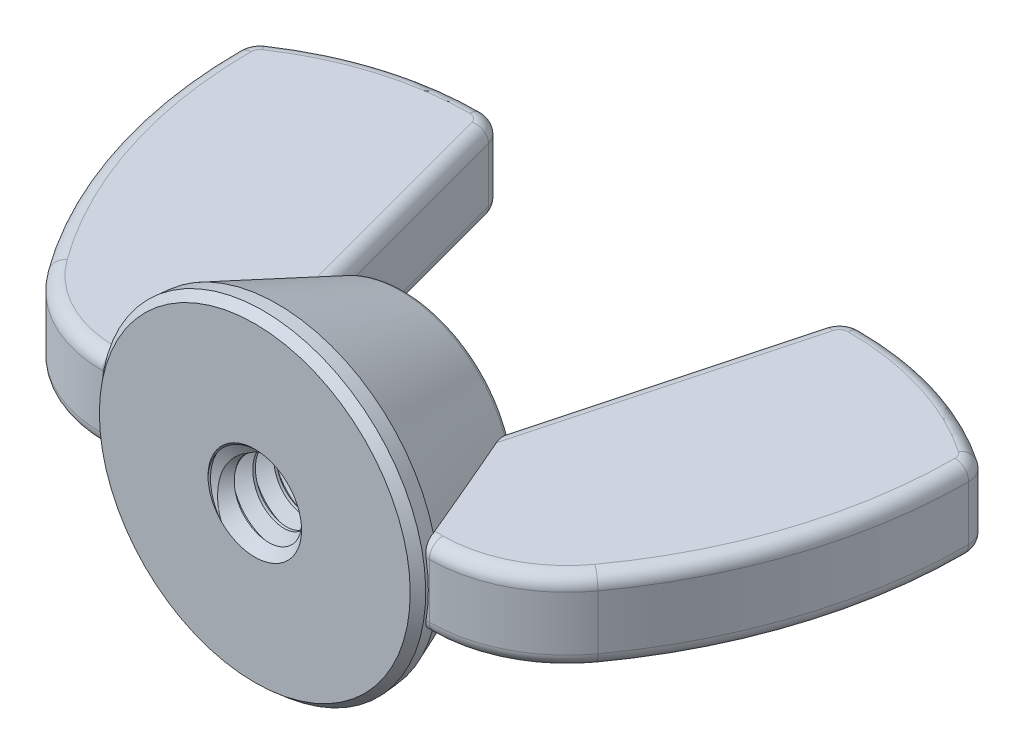
SolidWorks part; units mm, degrees
ref_plane "Front Plane" through (0, 0, 0) normal (0, 0, 1) x (1, 0, 0)
ref_plane "Top Plane" through (0, 0, 0) normal (0, 1, 0) x (1, 0, 0)
ref_plane "Right Plane" through (0, 0, 0) normal (1, 0, 0) x (0, 0, -1)
sketch "Sketch1" plane through (0, 0, 0) normal (0, 0, 1) x (1, 0, 0)
  circle A0 centre (0, 0) radius 1.4224
  circle A1 centre (0, 0) radius 4.9609
  dimension "D1" = 9.9219
sketch "Sketch2" plane through (0, 0, 0) normal (0, 1, 0) x (1, 0, 0)
  line L0 (0, 0) -> (0, 12.7) construction
  line L1 (-1.4224, 0) -> (1.4224, 0) construction
  line L2 (-11.1125, 12.7) -> (11.1125, 12.7) construction
  line L3 (11.1125, 12.7) -> (11.1125, 0) construction
  line L4 (-11.1125, 12.7) -> (-11.1125, 0) construction
  line L5 (-11.1125, 0) -> (11.1125, 0) construction
  line L6 (-3.3816, 4.572) -> (3.3816, 4.572) construction
  line L7 (0, 0) -> (0, 4.572) construction
  line L8 (-4.3144, 0.6858) -> (4.9609, 0.6858) construction
  line L9 (4.9609, 0) -> (4.9609, 4.572) construction
  line L10 (3.0435, 4.572) -> (5.2692, 12.8785)
  line L12 (3.3816, 4.572) -> (3.3816, 0.3429) construction
  line L13 (-4.9609, 0) -> (4.9609, 0) construction
  line L14 (4.9609, 0.6858) -> (3.3816, 4.572) construction
  line L15 (5.2692, 12.8785) -> (11.3534, 11.0184)
  line L16 (11.3534, 11.0184) -> (6.8784, 0.3429)
  line L17 (4.9609, 0.3429) -> (6.8784, 0.3429)
  line L19 (3.0435, 0.3429) -> (4.9609, 0.3429)
  line L20 (-3.0435, 4.572) -> (3.0435, 4.572) construction
  line L21 (3.0435, 4.572) -> (3.0435, 0.3429)
  circle A3 centre (10.4235, 10.5822) radius 0.689 construction
  circle A4 centre (5.7501, 12.011) radius 0.689 construction
  dimension "D6" = 1.378
  dimension "D2" = 4.572
  dimension "D4" = 6.7633
  dimension "D1" = 0.6858
  dimension "D3" = 22.116
  dimension "D5" = 0.3429
  dimension "D8" = 17
  dimension "D9" = 6.087
  dimension "D7" = 15
sketch "Sketch13" plane through (0, 0, 0) normal (0, 1, 0) x (1, 0, 0)
  line L1 (3.0435, 4.572) -> (3.0435, 0.3429) construction
  line L2 (3.0435, 4.572) -> (5.2692, 12.8785) construction
  line L3 (-11.1125, 12.7) -> (11.1125, 12.7) construction
  line L4 (11.1125, 12.7) -> (11.1125, 0) construction
  line L5 (4.9609, 0.3429) -> (6.8784, 0.3429) construction
  line L6 (3.0435, 0.3429) -> (4.9609, 0.3429) construction
  line L7 (0, 0) -> (0, 4.572) construction
  line L8 (-1.4224, 0) -> (1.4224, 0) construction
  line L9 (0, 0) -> (0, 12.7) construction
  line L10 (-3.3816, 4.572) -> (3.3816, 4.572) construction
  line L11 (3.0435, 0.3429) -> (4.9609, 0.3429)
  line L12 (3.0435, 4.572) -> (3.0435, 0.3429)
  line L13 (3.0435, 4.572) -> (5.0845, 12.1893)
  circle A0 centre (10.4235, 10.5822) radius 0.689 construction
  circle A1 centre (5.7501, 12.011) radius 0.689 construction
  arc A5 (11.1125, 10.5822) -> (10.8088, 11.1534) centre (10.4235, 10.5822) ccw
  arc A6 (5.7501, 12.7) -> (5.0845, 12.1893) centre (5.7501, 12.011) ccw
  arc A7 (8.3532, 2.0738) -> (11.1125, 10.5822) centre (-3.3853, 10.5822) ccw
  arc A8 (10.8088, 11.1534) -> (5.7501, 12.7) centre (5.7501, 3.6536) ccw
  arc A10 (4.9609, 0.3429) -> (8.3532, 2.0738) centre (4.9609, 4.5326) ccw
extrude "Extrude2" add sketch "Sketch13" along normal mid plane 2.4805
sketch "Sketch3" plane through (0, 0, 0) normal (0, 0, 1) x (1, 0, 0)
  circle A0 centre (0, 0) radius 4.9609 construction
  circle A1 centre (0, 0) radius 4.9609
extrude "Extrude1" add sketch "Sketch3" against normal up to vertex (0.6858 mm away) draft 5 separate body up to point (4.9609, 0, -0.6858)
sketch "Sketch15" plane through (0, 0, -0.6858) normal (0, 0, -1) x (-1, 0, 0)
  circle A1 centre (0, 0) radius 4.9009
  circle A2 centre (0, 0) radius 4.9009
  dimension "D1" = 0
extrude "Extrude3" add sketch "Sketch15" along normal up to vertex (3.8862 mm away) draft 22.116 up to point (0, 0, -4.572)
fillet "Fillet3" radius 0.254 1 edges at (-3.3216, 0, -4.572)
sketch "Sketch12" plane through (0, 0, -4.572) normal (0, 0, -1) x (-1, 0, 0)
  circle A1 centre (0, 0) radius 4.9009
  circle A2 centre (0, 0) radius 4.9009 construction
  dimension "D1" = 9.8019
sketch "Sketch4" plane through (0, 0, 0) normal (0, 0, 1) x (1, 0, 0)
  circle A0 centre (0, 0) radius 1.4224 construction
  circle A1 centre (0, 0) radius 1.4224
extrude "Cut-Extrude1" cut sketch "Sketch4" against normal through all
sketch "Sketch5" plane through (0, 0, 0) normal (0, 0, 1) x (1, 0, 0)
  circle A0 centre (0, 0) radius 1.4224 construction
  circle A1 centre (0, 0) radius 1.4224
curve "Helix/Spiral1" pitch 0.635 height 7.747 radius 1.4224 centre (0, 0, 0) axis (0, 0, -1) start towards (1, 0, 0) parameters "pitch"=0.635
sketch "Sketch6" plane through (0, 0, 0) normal (0, 1, 0) x (1, 0, 0)
  line L0 (-1.4224, -0.5556) -> (-1.01, -0.3175)
  line L1 (-1.01, -0.3175) -> (-1.01, -0.2381)
  line L2 (-1.01, -0.2381) -> (-1.4224, 0)
  line L3 (-1.4224, -0.5556) -> (-1.4224, 0)
  line L4 (-1.4224, -0.2778) -> (-1.01, -0.2778) construction
  line L5 (-1.2162, -0.4366) -> (-1.2162, -0.1191) construction
  line L6 (-1.4224, 0) -> (1.4224, 0) construction
  dimension "D1" = 60
  dimension "D2" = 0.0794
  dimension "D3" = 0.3175
sweep "Sweep1" add profiles "Sketch6" path "Helix/Spiral1"
sketch "Sketch7" plane through (0, 0, 0) normal (0, 0, 1) x (1, 0, 0)
  circle A1 centre (0, 0) radius 4.9609
  circle A2 centre (0, 0) radius 4.9609
  dimension "D1" = 0
extrude "Cut-Extrude2" cut sketch "Sketch7" along normal through all
ref_plane "Plane1" through (0, 0, -4.572) normal (0, 0, 1) x (1, 0, 0)
sketch "Sketch8" plane through (0, 0, -4.572) normal (0, 0, 1) x (1, 0, 0)
  circle A0 centre (0, 0) radius 4.9009 construction
  circle A2 centre (0, 0) radius 4.9009
extrude "Cut-Extrude3" cut sketch "Sketch8" against normal through all
sketch "Sketch9" plane through (0, 0, 0) normal (0, 0, 1) x (1, 0, 0)
  circle A1 centre (0, 0) radius 1.4224
  circle A2 centre (0, 0) radius 1.4224
  dimension "D1" = 0
extrude "Cut-Extrude4" cut sketch "Sketch9" against normal through all draft 45
sketch "Sketch11" plane through (0, 0, -4.572) normal (0, 0, 1) x (1, 0, 0)
  circle A0 centre (0, 0) radius 1.4224 construction
  circle A1 centre (0, 0) radius 1.3716
  circle A2 centre (0, 0) radius 1.4224 construction
  dimension "D1" = 0.0508
extrude "Cut-Extrude5" cut sketch "Sketch11" along normal through all draft 45
chamfer "Chamfer1" distance 0.2572 angle 45 1 edges at (4.9609, 0, 0) first distance on face at (-4.9009, 0, -0.6858)
fillet "Fillet4" radius 0.4134 14 edges at (4.0022, 1.2402, -0.3429) (6.8651, 1.2402, -0.8006) (5.3306, 1.2402, -12.5576) (8.395, 1.2402, -12.3047) (11.0318, 1.2402, -10.9057) (4.0022, -1.2402, -0.3429) (6.8651, -1.2402, -0.8006) (5.3306, -1.2402, -12.5576) (8.395, -1.2402, -12.3047) (11.0318, -1.2402, -10.9057) (10.4054, 1.2402, -6.1098) (10.4054, -1.2402, -6.1098) (4.064, 1.2402, -8.3807) (4.064, -1.2402, -8.3807)
mirror "Mirror6" about plane through (0, 0, 0) normal (1, 0, 0) of bodies 108 113
combine bodies "Combine2" operation type add bodies to combine 116 108 107
equation "\"D1@Sketch1\" = \"thread dia@Sketch1\"*1.725"
equation "\"D2@Sketch2\" = \"B@Sketch2\"*.36"
equation "\"D3@Helix/Spiral1\" = \"D2@Sketch2\"+.125"
equation "\"D2@Sketch6\" = \"pitch@Helix/Spiral1\"*.125"
equation "\"D3@Sketch6\" = \"pitch@Helix/Spiral1\"*.5"
equation "\"D4@Sketch2\" = \"D1@Sketch12\"*.69"
equation "\"D1@Extrude2\" = \"D1@Sketch1\"*.25"
equation "\"D1@Sketch2\" = \"D2@Sketch2\"*.150"
equation "\"D5@Sketch2\" = \"D1@Sketch2\"/2"
equation "\"D3@Extrude3\" = \"D3@Sketch2\""
equation "\"D1@Chamfer1\" = \"D5@Sketch2\"*.75"
equation "\"D9@Sketch2\" = \"D4@Sketch2\"*.9"
equation "\"D6@Sketch2\" = \"D1@Extrude2\"/1.8"
equation "\"D1@Fillet4\" = \"D1@Extrude2\"/6"
